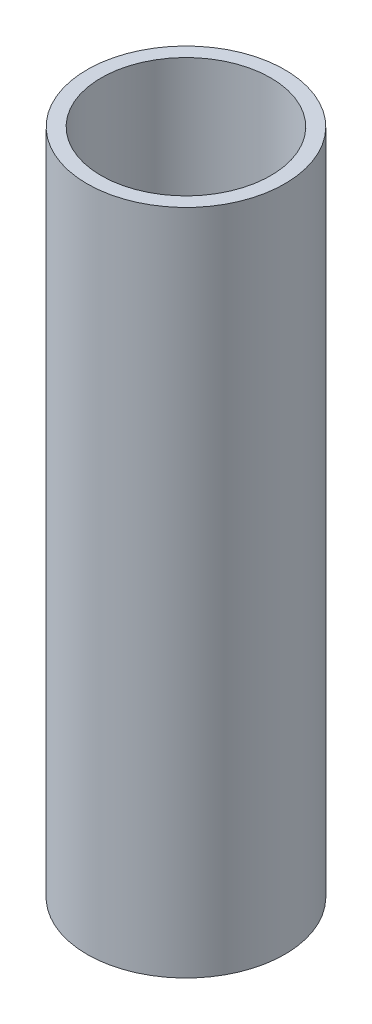
SolidWorks part; units mm, degrees
material "ABS PC"
ref_plane "Alzado" through (0, 0, 0) normal (0, 0, 1) x (1, 0, 0)
ref_plane "Planta" through (0, 0, 0) normal (0, 1, 0) x (1, 0, 0)
ref_plane "Vista lateral" through (0, 0, 0) normal (1, 0, 0) x (0, 0, -1)
sketch "Sketch1" plane through (0, 0, 0) normal (0, 1, 0) x (1, 0, 0)
  circle A0 centre (0, 0) radius 22.225
  circle A1 centre (0, 0) radius 19.05
  dimension "D1" = 44.45
  dimension "D2" = 38.1
extrude "Boss-Extrude1" add sketch "Sketch1" along normal blind 150
